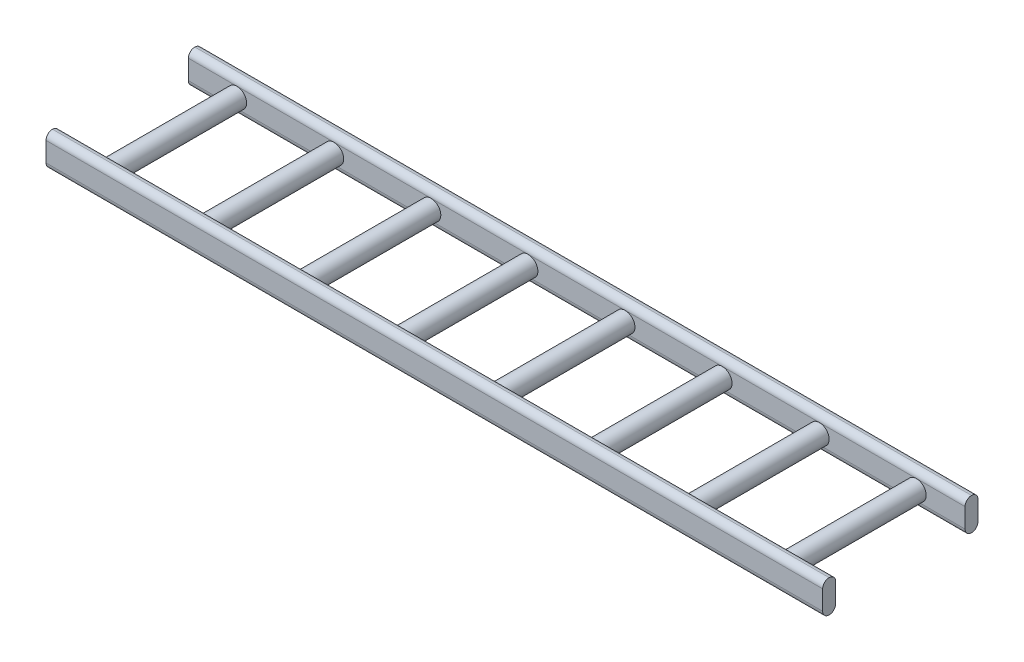
SolidWorks part; units mm, degrees
ref_plane "Front Plane" through (0, 0, 0) normal (0, 0, 1) x (1, 0, 0)
ref_plane "Top Plane" through (0, 0, 0) normal (0, 1, 0) x (1, 0, 0)
ref_plane "Right Plane" through (0, 0, 0) normal (1, 0, 0) x (0, 0, -1)
sketch "Sketch3" plane through (0, 0, 0) normal (0, 0, 1) x (1, 0, 0)
  line L1 (75, -25) -> (-75, -25)
  line L2 (75, -25) -> (75, 25)
  line L3 (75, 25) -> (-75, 25)
  line L4 (-75, -25) -> (-75, 25)
  line L5 (75, -25) -> (-75, 25) construction
  line L6 (75, 25) -> (-75, -25) construction
  point P0 (0, 0)
  dimension "D1" = 150
  dimension "D2" = 50
extrude "Boss-Extrude1" add sketch "Sketch3" along normal blind 20
sketch "Sketch4" plane through (0, 0, 20) normal (0, 0, 1) x (1, 0, 0)
  circle A0 centre (0, 0) radius 15
  dimension "D1" = 30
extrude "Boss-Extrude2" add sketch "Sketch4" along normal blind 200
sketch "Sketch5" plane through (0, 0, 220) normal (0, 0, 1) x (1, 0, 0)
  line L1 (75, 25) -> (-75, 25)
  line L2 (75, 25) -> (75, -25)
  line L3 (75, -25) -> (-75, -25)
  line L4 (-75, 25) -> (-75, -25)
  line L5 (75, 25) -> (-75, -25) construction
  line L6 (75, -25) -> (-75, 25) construction
  point P0 (0, 0)
extrude "Boss-Extrude3" add sketch "Sketch5" along normal blind 20
mirror "Mirror1" about plane through (75, -25, 20) normal (-1, 0, 0) of bodies 103
mirror "Mirror2" about plane through (225, 25, 240) normal (-1, 0, 0) of bodies 104
mirror "Mirror3" about plane through (525, 25, 240) normal (-1, 0, 0) of bodies 105
fillet "Fillet2" radius 10 8 edges at (525, -25, 20) (525, -25, 0) (525, 25, 0) (525, 25, 20) (525, 25, 220) (525, 25, 240) (525, -25, 220) (525, -25, 240)
